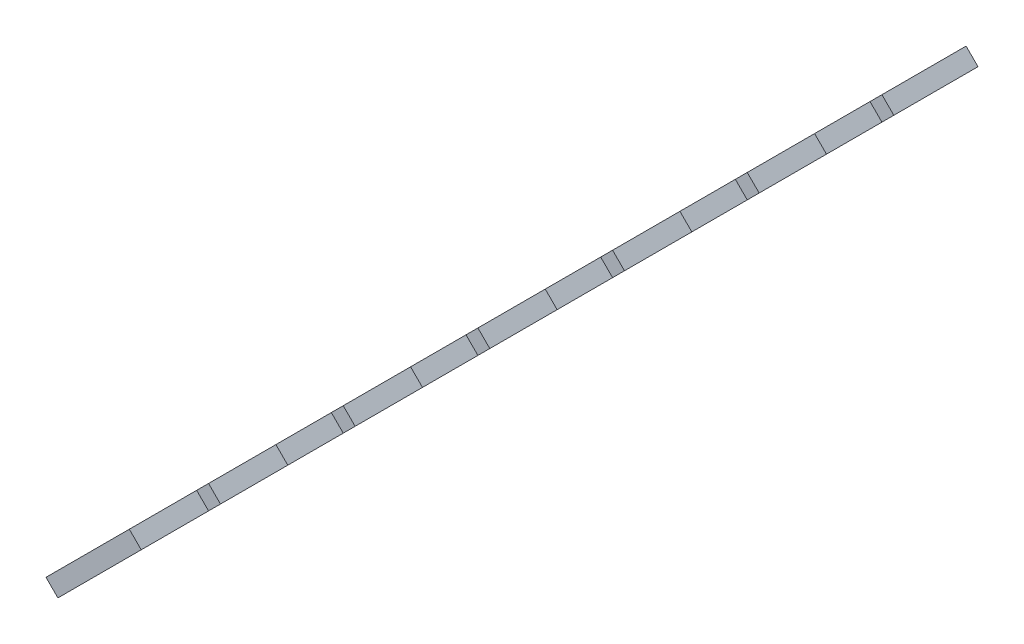
SolidWorks part; units mm, degrees
ref_plane "Front Plane" through (0, 0, 0) normal (0, 0, 1) x (1, 0, 0)
ref_plane "Top Plane" through (0, 0, 0) normal (0, 1, 0) x (1, 0, 0)
ref_plane "Right Plane" through (0, 0, 0) normal (1, 0, 0) x (0, 0, -1)
sketch "Sketch1" plane through (0, 0, 0) normal (0, 0, 1) x (1, 0, 0)
  line L0 (91.6648, 29.3027) -> (52.5461, -9.816) construction
  line L2 (78.5772, 20.7053) -> (74.1015, 16.2295) construction
  line L3 (78.5917, 11.7394) -> (83.0674, 16.2151) construction
  line L4 (39.9621, 9.9289) -> (35.472, 14.4191)
  line L5 (39.9621, 9.9289) -> (71.393, 41.3598)
  line L6 (35.472, 14.4191) -> (66.9029, 45.85)
  line L7 (71.393, 41.3598) -> (66.9029, 45.85)
  line L8 (108.2121, 4.5408) -> (76.7812, -26.8901) construction
  line L9 (76.7812, -26.8901) -> (72.2911, -22.4) construction
  line L10 (103.722, 9.0309) -> (72.2911, -22.4) construction
extrude "Boss-Extrude1" add sketch "Sketch1" along normal up to surface (304.8 mm away)
sketch "Sketch2" plane through (56.3764, 56.3764, 0) normal (0.7071, 0.7071, 0) x (0, 0, -1)
  line L0 (-304.8, -21.2367) -> (0, -21.2367) construction
  line L1 (-279.4, -21.2367) -> (-254, -21.2367)
  line L2 (-279.4, -21.2367) -> (-279.4, -14.8867)
  line L3 (-279.4, -14.8867) -> (-254, -14.8867)
  line L4 (-254, -21.2367) -> (-254, -14.8867)
  line L5 (-304.8, -14.8867) -> (0, -14.8867) construction
  dimension "D1" = 25.4
  dimension "D2" = 25.4
extrude "Boss-Extrude2" add sketch "Sketch2" along normal blind 6.35
pattern_linear "LPattern1" count 6 spacing 50.8 along (0, 0, -1) of "Boss-Extrude2"
sketch "Sketch3" plane through (15.0166, -15.0166, 0) normal (0.7071, -0.7071, 0) x (0, 0, -1)
  circle A0 centre (-273.3375, 57.5033) radius 2.8702
extrude "Cut-Extrude1" cut sketch "Sketch3" against normal up to surface (6.35 mm away) up to face at (66.7302, 45.6773, 155.3308)
sketch "Sketch4" plane through (0, 0, 0) normal (0, 0, -1) x (-1, 0, 0)
  line L0 (-35.472, 14.4191) -> (-39.9621, 9.9289)
  line L1 (-71.393, 50.3401) -> (-35.472, 14.4191) construction
  line L2 (-39.9621, 9.9289) -> (-75.8832, 45.85) construction
  line L3 (-39.9621, 9.9289) -> (-48.9424, 18.9092)
  line L4 (-48.9424, 18.9092) -> (-44.4523, 23.3993)
  line L5 (-44.4523, 23.3993) -> (-35.472, 14.4191)
  dimension "D1" = 12.7
  dimension "D2" = 0
  dimension "D3" = 6.35
extrude "Boss-Extrude3" add sketch "Sketch4" along normal blind 6.35
pattern_linear "LPattern2" count 2 spacing 38.1 along (0.7071, 0.7071, 0) of "Boss-Extrude3"
sketch "Sketch5" plane through (10.5265, -10.5265, 0) normal (-0.7071, 0.7071, 0) x (0.7071, 0.7071, 0)
  line L0 (60.6783, -7.2251) -> (60.6783, -39.5117) construction
  line L1 (47.9783, 6.35) -> (47.9783, 0) construction
  line L2 (73.3783, 6.35) -> (73.3783, 0) construction
  line L3 (73.3783, 0) -> (47.9783, 0) construction
  line B0 (62.8119, 0) -> (58.5447, 0)
  line B1 (58.5447, -11.938) -> (56.2333, -11.938)
  line B2 (56.2333, -11.938) -> (56.2333, -8.763)
  line B3 (56.2333, -8.763) -> (58.5447, -8.763)
  line B4 (58.5447, -8.763) -> (58.5447, 0)
  line B5 (58.5447, -11.938) -> (58.5447, -15.24)
  line B6 (58.5447, -15.24) -> (62.8119, -15.24)
  line B7 (62.8119, -11.938) -> (62.8119, -15.24)
  line B8 (62.8119, -8.763) -> (62.8119, 0)
  line B9 (65.1233, -8.763) -> (62.8119, -8.763)
  line B10 (65.1233, -11.938) -> (65.1233, -8.763)
  line B11 (62.8119, -11.938) -> (65.1233, -11.938)
sketch_block_instance "TSlot-1"
sketch_block "TSlot" parameters "D1"=3.302, "D2"=3.175
extrude "Cut-Extrude2" cut sketch "Sketch5" against normal through all
